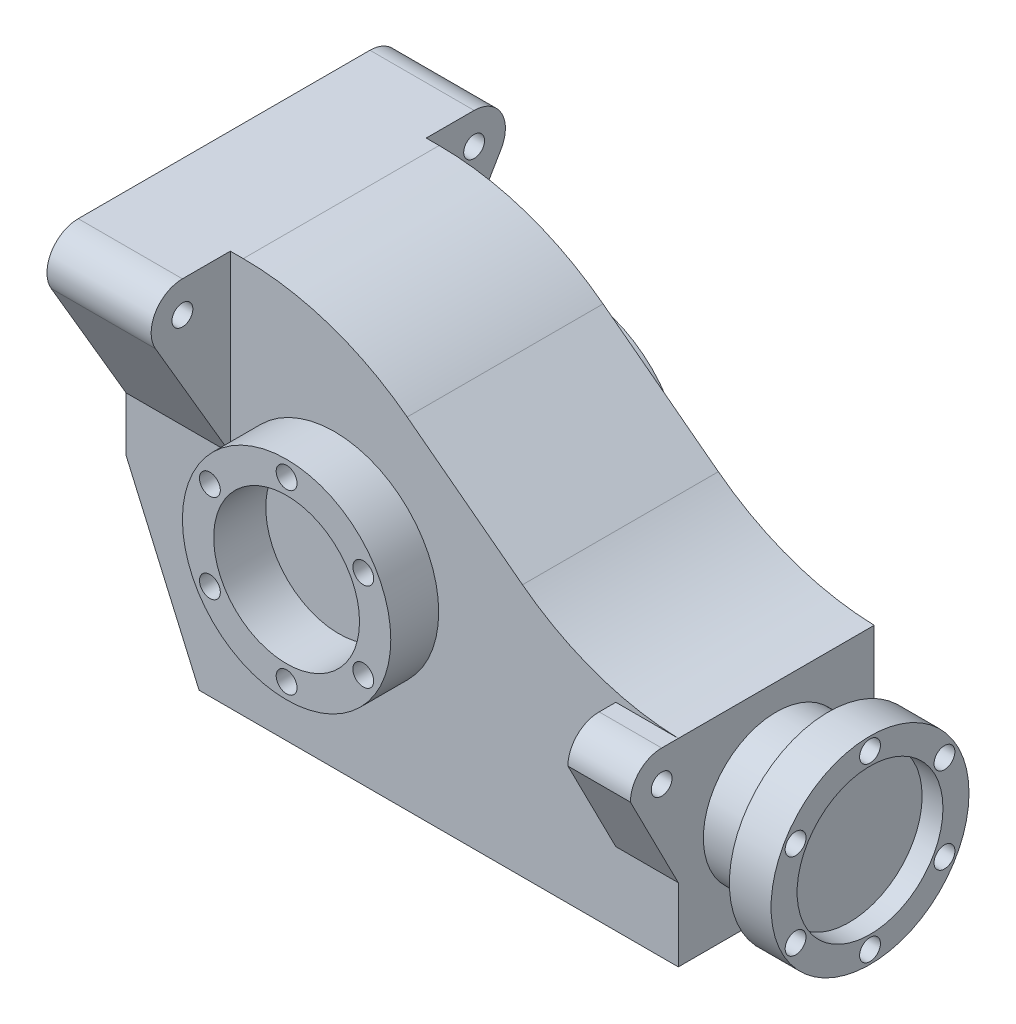
SolidWorks part; units mm, degrees
ref_plane "Płaszczyzna przednia" through (0, 0, 0) normal (0, 0, 1) x (1, 0, 0)
ref_plane "Płaszczyzna górna" through (0, 0, 0) normal (0, 1, 0) x (1, 0, 0)
ref_plane "Płaszczyzna prawa" through (0, 0, 0) normal (1, 0, 0) x (0, 0, -1)
sketch "Szkic1" plane through (0, 0, 0) normal (0, 0, 1) x (1, 0, 0)
  line L0 (-35, 190) -> (65, 190)
  line L1 (65, 190) -> (190, 95)
  line L2 (190, 95) -> (230, 95)
  line L3 (230, 95) -> (230, 0)
  line L4 (230, 0) -> (0, 0)
  line L7 (-35, 190) -> (-35, 80)
  line L8 (-35, 80) -> (0, 0)
  dimension "D1" = 265
  dimension "D2" = 190
  dimension "D3" = 95
  dimension "D4" = 80
  dimension "D5" = 230
  dimension "D6" = 100
  dimension "D7" = 40
extrude "Dodanie-wyciągnięcie1" add sketch "Szkic1" along normal mid plane 94 contours L1 L2 L3 L4 L8 L7 L0
sketch "Szkic2" plane through (230, 0, 0) normal (1, 0, 0) x (0, 0, -1)
  line L0 (-47, 95) -> (47, 0) construction
  line L1 (47, 95) -> (-47, 0) construction
  line L2 (-47, 0) -> (47, 0) construction
  circle A0 centre (0, 47.5) radius 35
  point P13 (0, 47.5)
  dimension "D1" = 70
extrude "Dodanie-wyciągnięcie2" add sketch "Szkic2" along normal blind 25 separate body
sketch "Szkic3" plane through (255, 0, 0) normal (1, 0, 0) x (0, 0, -1)
  circle A0 centre (0, 47.5) radius 47.5
  circle A1 centre (0, 47.5) radius 35 construction
  dimension "D1" = 95
extrude "Dodanie-wyciągnięcie3" add sketch "Szkic3" along normal blind 20
sketch "Szkic4" plane through (275, 0, 0) normal (1, 0, 0) x (0, 0, -1)
  circle A0 centre (0, 47.5) radius 35
  circle A1 centre (0, 47.5) radius 47.5 construction
  dimension "D1" = 70
sketch "Szkic7" plane through (0, 0, 47) normal (0, 0, 1) x (1, 0, 0)
  line L0 (-35, 190) -> (-35, 80) construction
  line L1 (-35, 190) -> (65, 190) construction
  circle A0 centre (65, 90) radius 50
  dimension "D1" = 100
  dimension "D2" = 100
  dimension "D3" = 100
extrude "Dodanie-wyciągnięcie5" add sketch "Szkic7" along normal blind 23
sketch "Szkic8" plane through (0, 0, 70) normal (0, 0, 1) x (1, 0, 0)
  circle A0 centre (65, 90) radius 35
  dimension "D1" = 70
extrude "Wytnij-wyciągnięcie1" cut sketch "Szkic8" against normal blind 25
sketch "Szkic9" plane through (0, 0, 70) normal (0, 0, 1) x (1, 0, 0)
  line L0 (65, 90) -> (65, 132.5) construction
  circle A0 centre (65, 132.5) radius 5
  circle A1 centre (101.8061, 111.25) radius 5
  circle A2 centre (65, 90) radius 35 construction
  circle A3 centre (65, 90) radius 35
  circle A4 centre (101.8061, 68.75) radius 5
  circle A5 centre (65, 47.5) radius 5
  circle A6 centre (28.1939, 68.75) radius 5
  circle A7 centre (28.1939, 111.25) radius 5
  dimension "D1" = 10
  dimension "D2" = 42.5
  dimension "D3" = 6
  dimension "D4" = 42.5
extrude "Wytnij-wyciągnięcie2" cut sketch "Szkic9" against normal blind 15 contours A0 | A1 | A4 | A5 | A6 | A7
sketch "Szkic12" plane through (-35, 0, 0) normal (-1, 0, 0) x (0, 0, 1)
  line L0 (-70, 190) -> (70, 190)
  line L1 (47, 190) -> (-47, 190) construction
  line L2 (-82.9419, 167.4166) -> (-20, 60)
  line L4 (47, 0) -> (-47, 0) construction
  line L5 (-20, 60) -> (20, 60)
  line L6 (0, 190) -> (0, 60) construction
  line L7 (82.9419, 167.4166) -> (20, 60)
  circle A0 centre (-70, 175) radius 5
  arc A1 (-70, 190) -> (-82.9419, 167.4166) centre (-70, 175) ccw
  arc A2 (70, 190) -> (82.9419, 167.4166) centre (70, 175) cw
  circle A3 centre (70, 175) radius 5
  line M4 (-47, 190) -> (-47, 80)
  line M5 (-47, 80) -> (47, 80)
  line M6 (47, 80) -> (47, 190)
  line M7 (47, 190) -> (-47, 190)
  dimension "D1" = 10
  dimension "D2" = 30
  dimension "D4" = 20
  dimension "D5" = 70
  dimension "D3" = 60
extrude "Dodanie-wyciągnięcie6" add sketch "Szkic12" against normal blind 50 contours L0 A1 L2 A0 M4 | L6 L0 L2 M4 M5 | L6 L7 M7 M5 M6 | A2 L0 L7 A3 M6 | L6 L5 L7 M5 | L6 L2 L5 M5 region at (-35, 159.5519, -61.1328) region at (-35, 136.8562, -22.7622) region at (-35, 136.8562, 22.7622) region at (-35, 159.5519, 61.1328) region at (-35, 70.7553, 13.1511) region at (-35, 70.7553, -13.1511)
mirror "Lustro1" about plane through (0, 0, 0) normal (0, 0, 1) of "Wytnij-wyciągnięcie2", "Wytnij-wyciągnięcie1", "Dodanie-wyciągnięcie5"
fillet "Zaokrąglenie2" radius 130 1 edges at (65, 190, 0)
fillet "Zaokrąglenie3" radius 130 1 edges at (190, 95, 0)
extrude "Wytnij-wyciągnięcie3" cut sketch "Szkic4" against normal blind 10
sketch "Szkic13" plane through (0, 0, 47) normal (0, 0, 1) x (1, 0, 0)
  line L0 (230, 95) -> (230, 0) construction
  line L1 (230, 95) -> (200, 95)
  line L2 (230, 95) -> (230, 35)
  line L3 (230, 35) -> (200, 35)
  line L4 (200, 95) -> (200, 35)
  dimension "D1" = 60
  dimension "D2" = 30
sketch "Szkic14" plane through (0, 0, 70) normal (0, 0, 1) x (1, 0, 0)
  line L1 (200, 95) -> (230, 95)
  line L2 (200, 95) -> (200, 60)
  line L3 (200, 60) -> (230, 60)
  line L4 (230, 95) -> (230, 60)
  line L5 (230, 95) -> (230, 35) construction
  dimension "D1" = 35
loft "Wyciągnięcie po profilach1" add profiles "Szkic13", "Szkic14" connector at (230, 35, 47) connector at (230, 60, 70)
sketch "Szkic15" plane through (230, 0, 0) normal (1, 0, 0) x (0, 0, -1)
  line L0 (-47, 95) -> (-70, 95) construction
  line L1 (-70, 60) -> (-70, 95) construction
  line L5 (-70, 80) -> (-70, 95)
  line L6 (-70, 95) -> (-55, 95)
  arc A0 (-55, 95) -> (-70, 80) centre (-55, 80) ccw
  dimension "D1" = 30
extrude "Wytnij-wyciągnięcie4" cut sketch "Szkic15" against normal up to next (30 mm away)
sketch "Szkic19" plane through (230, 0, 0) normal (1, 0, 0) x (0, 0, -1)
  line L0 (-70, 80) -> (-47, 35)
  line L1 (-47, 35) -> (-70, 60)
  line L2 (-70, 60) -> (-70, 80)
extrude "Wytnij-wyciągnięcie6" cut sketch "Szkic19" against normal up to next (30 mm away) contours L0 L1 L2
sketch "Szkic20" plane through (230, 0, 0) normal (1, 0, 0) x (0, 0, -1)
  circle A0 centre (-55, 80) radius 5
  arc A1 (-55, 95) -> (-70, 80) centre (-55, 80) ccw construction
  dimension "D1" = 10
extrude "Wytnij-wyciągnięcie7" cut sketch "Szkic20" against normal up to next (30 mm away)
sketch "Szkic21" plane through (275, 0, 0) normal (1, 0, 0) x (0, 0, -1)
  circle A0 centre (0, 88.75) radius 5
  circle A3 centre (0, 47.5) radius 35 construction
  dimension "D1" = 10
  dimension "D2" = 41.25
extrude "Wytnij-wyciągnięcie8" cut sketch "Szkic21" against normal blind 10
pattern_circular "Szyk kołowy1" count 6 over 360 about axis through (265, 47.5, 0) along (1, 0, 0) of "Wytnij-wyciągnięcie8"
